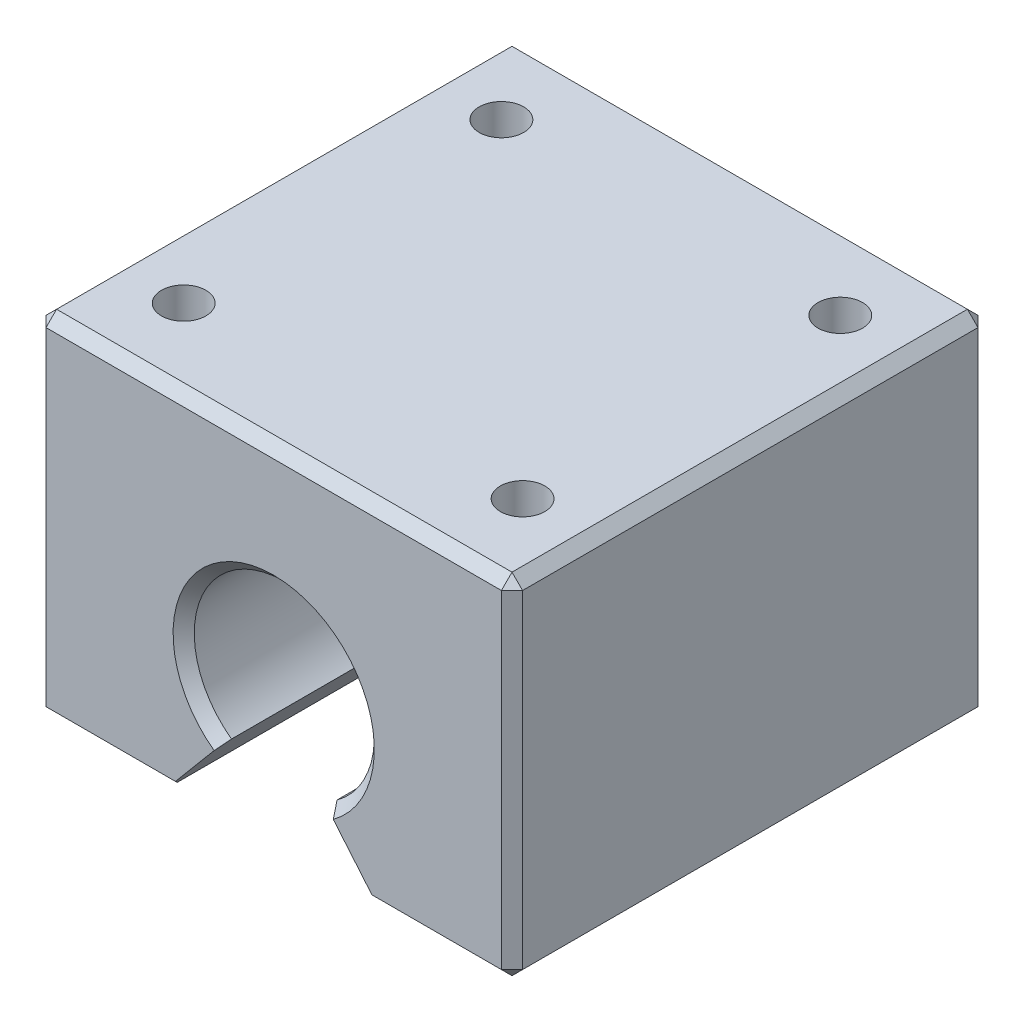
SolidWorks part; units mm, degrees
note: '?' marks a value the reader was unsure of.
material "1060 Alloy"
ref_plane "Front" through (0, 0, 0) normal (0, 0, 1) x (1, 0, 0)
ref_plane "Top" through (0, 0, 0) normal (0, 1, 0) x (1, 0, 0)
ref_plane "Right" through (0, 0, 0) normal (1, 0, 0) x (0, 0, -1)
ref_axis "Axis1" through (-84.4107, 0, 0) along (1, 0, 0)?
ref_axis "Axis2" through (0, 64.3378, 0) along (0, -1, 0)?
ref_axis "Axis3" through (0, 0, -102.329) along (0, 0, 1)?
sketch "Sketch1" plane through (0, 0, 0) normal (0, 0, 1) x (1, 0, 0)
  line L1 (-22.5, -16.5) -> (22.5, -16.5)
  line L2 (-22.5, -16.5) -> (-22.5, 16.5)
  line L3 (-22.5, 16.5) -> (22.5, 16.5)
  line L4 (22.5, -16.5) -> (22.5, 16.5)
  line L5 (-22.5, -16.5) -> (22.5, 16.5) construction
  line L6 (-22.5, 16.5) -> (22.5, -16.5) construction
  point P0 (0, 0)
  dimension "D1" = 45
  dimension "D2" = 33
extrude "Extrude1" add sketch "Sketch1" along normal blind 45
sketch "Sketch2" plane through (0, 0, 45) normal (0, 0, 1) x (1, 0, 0)
  line L0 (22.5, 16.5) -> (-22.5, 16.5) construction
  line L1 (0, -4.4474) -> (-13.5396, -20.5832)
  line L2 (-13.5396, -20.5832) -> (13.5396, -20.5832)
  line L3 (13.5396, -20.5832) -> (0, -4.4474)
  line L4 (-22.5, 16.5) -> (-22.5, -16.5) construction
  line L5 (5, -4.1137) -> (5, -15.1699) construction
  line L6 (-5, -4.1137) -> (-5, -15.1699) construction
  line L7 (-5, -4.1137) -> (0, -4.1137) construction
  line L8 (0, -4.1137) -> (5, -4.1137) construction
  circle A0 centre (0, -3.5) radius 8.5
  point P6 (-22.5, 0)
  line M4 (-22.5, -16.5) -> (22.5, -16.5)
  dimension "D1" = 17
  dimension "D2" = 20
  dimension "D3" = 80
  dimension "D4" = 22.5
  dimension "D5" = 5
extrude "Extrude3" cut sketch "Sketch2" against normal through all contours L3 A0 L1 | L1 A0 L3 | L2 L3 L1 M4 | A0 L1 L3 M4
hole_wizard "M5 Tapped Hole1" positions "Sketch4" profile "Sketch3" tap size "M5" standard "ISO"
sketch "Sketch4" plane through (0, 16.5, 0) normal (0, 1, 0) x (-1, 0, 0)
  line L1 (16, 0.1308) -> (16, 38.7595) construction
  line L4 (-16, 4.1131) -> (-16, 41.5128) construction
  line L7 (16, 7.5) -> (-26.0273, 7.5) construction
  line L13 (16, 37.5) -> (-21.414, 37.5) construction
  line L16 (-22.5, 0) -> (22.5, 0) construction
  line L17 (22.5, 45) -> (22.5, 0) construction
  point P0 (16, 7.5)
  point P1 (-16, 7.5)
  point P3 (-16, 37.5)
  point P5 (16, 37.5)
  dimension "D1" = 30
  dimension "D2" = 7.5
  dimension "D3" = 32
  dimension "D4" = 6.5
sketch "Sketch3" plane through (-16, 16.5, 7.5) normal (1, 0, 0) x (0, 0, 1)
  line L0 (0, 0) -> (0, 11.2618)
  line L1 (0, 11.2618) -> (2.1, 10)
  line L2 (2.1, 10) -> (2.1, 0)
  line L5 (2.1, 0) -> (0, 0)
  line L10 (0, 11.2618) -> (-2.1, 10) construction
  line L11 (0, -6.35) -> (0, 107.95) construction
  dimension "Tap Drill Dia." = 4.2
  dimension "Tap Drill Depth" = 10
  dimension "Drill Angle" = 118
cosmetic thread "Hole Thread1" parameters "D1"=9, "D2"=5
cosmetic thread "Hole Thread2" parameters "D1"=9, "D2"=5
cosmetic thread "Hole Thread3" parameters "D1"=9, "D2"=5
cosmetic thread "Hole Thread4" parameters "D1"=9, "D2"=5
chamfer "Chamfer1" distance 1 angle 45 16 edges at (0, 5, 0) (0, 5, 45) (16.3067, -16.5, 45) (-16.3067, -16.5, 45) (-22.5, -16.5, 22.5) (-16.3067, -16.5, 0) (22.5, -16.5, 22.5) (16.3067, -16.5, 0) (-22.5, 0, 0) (0, 16.5, 0) (-22.5, 0, 45) (22.5, 0, 45) (-22.5, 16.5, 22.5) (0, 16.5, 45) (22.5, 16.5, 22.5) (22.5, 0, 0)
